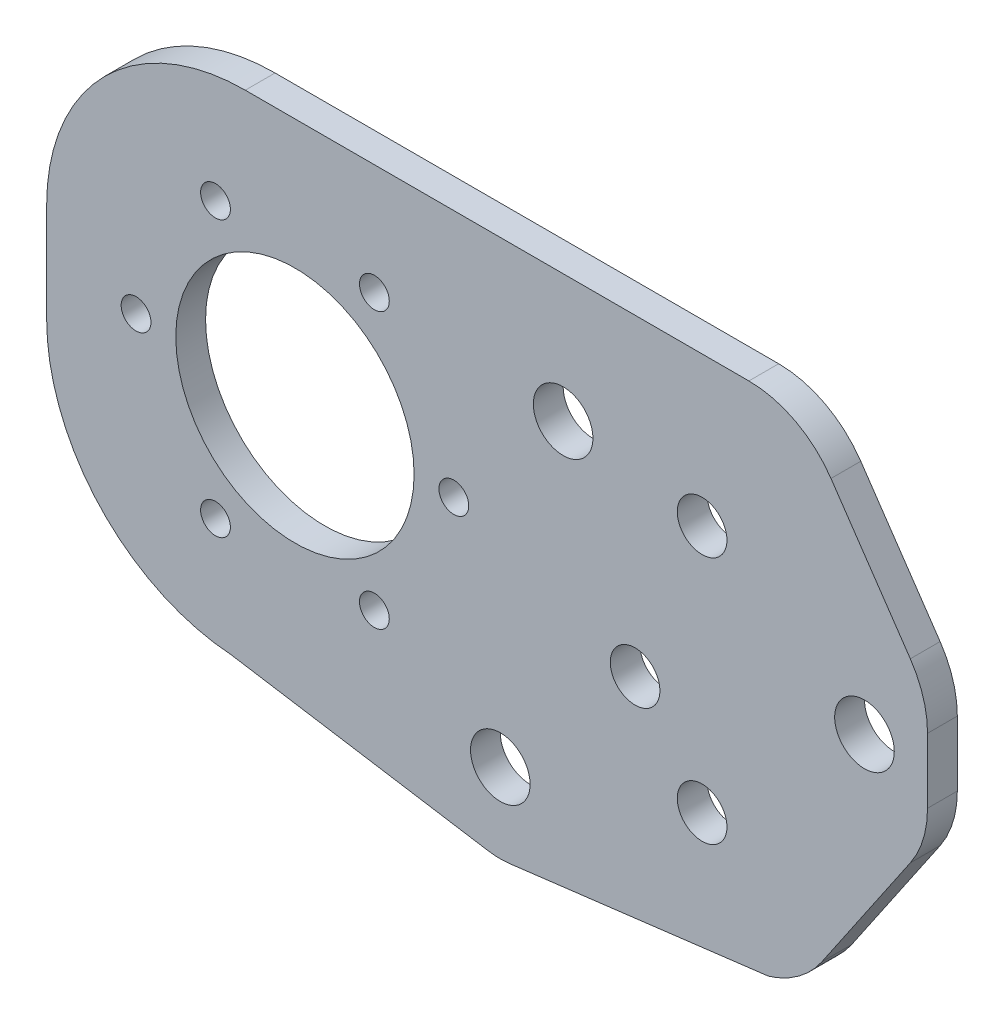
SolidWorks part; units mm, degrees
material "Gerais  - 6061-T6"
ref_plane "Plano frontal" through (0, 0, 0) normal (0, 0, 1) x (1, 0, 0)
ref_plane "Plano superior" through (0, 0, 0) normal (0, 1, 0) x (1, 0, 0)
ref_plane "Plano direito" through (0, 0, 0) normal (1, 0, 0) x (0, 0, -1)
sketch "Esboço1" plane through (0, 0, 0) normal (0, 0, 1) x (1, 0, 0)
  line L0 (56, 50) -> (56, 0) construction
  line L1 (0, 0) -> (76, 0)
  line L2 (0, 0) -> (0, 50)
  line L3 (0, 50) -> (76, 50)
  line L4 (76, 0) -> (76, 50)
  line L5 (66, 50) -> (66, 18.5) construction
  line L6 (65.25, 50) -> (65.25, 18.5) construction
  line L7 (59.25, 12.5) -> (25, 12.5) construction
  circle A0 centre (25, 25) radius 16 construction
  circle A1 centre (59.25, 18.5) radius 9.75 construction
  circle A2 centre (59.25, 18.5) radius 6 construction
  circle A3 centre (25, 25) radius 12.5 construction
  circle A4 centre (59.25, 18.5) radius 2.5
  circle A5 centre (25, 25) radius 12
  circle A6 centre (17, 38.8564) radius 1.5
  circle A7 centre (33, 38.8564) radius 1.5
  circle A8 centre (41, 25) radius 1.5
  circle A9 centre (33, 11.1436) radius 1.5
  circle A10 centre (17, 11.1436) radius 1.5
  circle A11 centre (9, 25) radius 1.5
  point P7 (41, 25)
  point P36 (25, 25)
  dimension "D1" = 32
  dimension "D5" = 12
  dimension "D6" = 19.5
  dimension "D9" = 25
  dimension "D10" = 5
  dimension "D13" = 24
  dimension "D14" = 3
  dimension "D2" = 25
  dimension "D3" = 35
  dimension "D4" = 20
  dimension "D7" = 0.75
  dimension "D8" = 10
  dimension "D11" = 25
  dimension "D12" = 50
  dimension "D15" = 6
extrude "Ressalto-extrusão1" add sketch "Esboço1" along normal blind 3
sketch "Esboço2" plane through (0, 0, 3) normal (0, 0, 1) x (1, 0, 0)
  line L0 (66, 50) -> (66, 0) construction
  line L1 (76, 50) -> (0, 50) construction
  line L2 (0, 0) -> (76, 0) construction
  line L3 (76, 0) -> (76, 50) construction
  circle A0 centre (66, 35) radius 2.5
  circle A1 centre (66, 15) radius 2.5
  dimension "D2" = 5
  dimension "D3" = 5
  dimension "D1" = 10
  dimension "D4" = 15
  dimension "D5" = 15
extrude "Corte-extrusão1" cut sketch "Esboço2" against normal blind 3
fillet "Filete1" radius 20 2 edges at (0, 0, 1.5) (0, 50, 1.5)
sketch "Esboço3" plane through (0, 0, 3) normal (0, 0, 1) x (1, 0, 0)
  circle A0 centre (66, 15) radius 2.5 construction
  circle A1 centre (66, 35) radius 2.5 construction
  circle A2 centre (66, 15) radius 2.5
  circle A3 centre (66, 35) radius 2.5
extrude "Ressalto-extrusão2" add sketch "Esboço3" against normal through all
sketch "Esboço5" plane through (0, 0, 0) normal (0, 0, -1) x (-1, 0, 0)
  circle A1 centre (-48, 43.65) radius 3 construction
  circle A2 centre (-45.6807, 3.8073) radius 3
  circle A3 centre (-48, 43.65) radius 3 construction
  circle A4 centre (-52.0071, 37.1424) radius 3
  circle A5 centre (-25, 25) radius 29.6112 construction
  circle A6 centre (-59.25, 18.5) radius 11 construction
  point P1 (-45.6808, 3.8073)
  dimension "D1" = 22
  dimension "D2" = 20
  dimension "D3" = 20
extrude "Corte-extrusão2" cut sketch "Esboço5" against normal through all
sketch "Esboço4" plane through (0, 0, 0) normal (0, 0, -1) x (-1, 0, 0)
  line L0 (-20, 0) -> (-76, 0) construction
  line L1 (-20, 0) -> (-76, 0)
  line L2 (-72.6649, -0.9251) -> (-46.6606, -4.1338)
  line L3 (-44.4129, -4.0929) -> (-15.4797, 0.5503)
  line L5 (-78.9768, 45.6286) -> (-86.9656, 33.897)
  line L6 (-73.1059, -0.8046) -> (-50.0089, -7.2259)
  line L7 (-46.1556, -7.2697) -> (-15.0816, 0.6142)
  line L8 (0, 20) -> (0, 30)
  line L9 (-20, 50) -> (-70.7112, 50)
  line L13 (0, 20) -> (0, 30)
  line L14 (-20, 50) -> (-70.7112, 50)
  line L28 (-78.9768, 45.6286) -> (-86.9656, 33.897)
  line L29 (-88.7, 28.2685) -> (-88.7, 21.7315)
  line L30 (-88.7, 28.2685) -> (-88.7, 21.7315)
  line L31 (-86.9656, 16.103) -> (-78.0603, 3.0256)
  line L32 (-86.9656, 16.103) -> (-78.0603, 3.0256)
  line L42 (-76, 0.8122) -> (-76, 0.7319)
  line L43 (-76, 0.8122) -> (-76, 0.7319)
  arc A0 (-78.0603, 3.0256) -> (-72.6649, -0.9251) centre (-69.7947, 8.6541) ccw
  arc A1 (-15.4797, 0.5503) -> (-14.5787, 0.7488) centre (-16.7476, 8.4505) ccw
  arc A2 (-46.6606, -4.1338) -> (-44.4129, -4.0929) centre (-45.6807, 3.8073) ccw
  arc A3 (-50.0089, -7.2259) -> (-46.1556, -7.2697) centre (-48, 0) ccw
  arc A4 (-15.0816, 0.6142) -> (0, 20) centre (-20, 20) ccw
  arc A5 (0, 30) -> (-20, 50) centre (-20, 30) ccw
  arc A7 (-14.5787, 0.7488) -> (0, 20) centre (-20, 20) ccw
  arc A8 (0, 30) -> (-20, 50) centre (-20, 30) ccw
  arc A22 (-70.7112, 50) -> (-78.9768, 45.6286) centre (-70.7112, 40) ccw
  arc A23 (-70.7112, 50) -> (-78.9768, 45.6286) centre (-70.7112, 40) ccw
  arc A24 (-86.9656, 33.897) -> (-88.7, 28.2685) centre (-78.7, 28.2685) ccw
  arc A25 (-86.9656, 33.897) -> (-88.7, 28.2685) centre (-78.7, 28.2685) ccw
  arc A26 (-88.7, 21.7315) -> (-86.9656, 16.103) centre (-78.7, 21.7315) ccw
  arc A27 (-88.7, 21.7315) -> (-86.9656, 16.103) centre (-78.7, 21.7315) ccw
  arc A58 (-78.0603, 3.0256) -> (-76, 0.8122) centre (-69.7947, 8.6541) ccw
  arc A60 (-76, 0.7319) -> (-73.1059, -0.8046) centre (-70.3513, 7.878) ccw
  point P25 (-45.6807, 3.8073)
  point P26 (-45.5353, -4.1927)
  line M13 (-76, 0) -> (-20, 0)
  arc M14 (-20, 0) -> (0, 20) centre (-20, 20) ccw
  dimension "D2" = 8
  dimension "D1" = 0
extrude "Ressalto-extrusão3" add sketch "Esboço4" against normal through all contours M14 M13 region at (47.6867, -1.4435, 0)
sketch "Esboço6" plane through (0, 0, 3) normal (0, 0, 1) x (1, 0, 0)
  line L0 (76, 50) -> (88.7, 31.35)
  line L1 (88.7, 31.35) -> (88.7, 18.65)
  line L2 (88.7, 18.65) -> (76, 0)
  line L3 (76, 0) -> (76, 50) construction
  line L4 (25, 25) -> (88.7, 25) construction
  circle A0 centre (82.35, 25) radius 3
  line M6 (76, 0) -> (76, 50)
  dimension "D2" = 6
  dimension "D3" = 12.7
  dimension "D4" = 6.35
extrude "Ressalto-extrusão4" add sketch "Esboço6" against normal through all contours L4 A0 L1 L0 M6 | L4 L2 L1 A0 M6 region at (80.9945, 34.3345, 3) region at (80.9945, 15.6655, 3)
fillet "Filete2" radius 10 4 edges at (88.7, 18.65, 1.5) (88.7, 31.35, 1.5) (76, 50, 1.5) (76, 0, 1.5)
sketch "Esboço7" plane through (0, 0, 3) normal (0, 0, 1) x (1, 0, 0)
  circle A0 centre (66, 35) radius 2.5
  circle A1 centre (66, 10) radius 2.5
  circle A2 centre (25, 25) radius 12 construction
  dimension "D1" = 5
  dimension "D2" = 25
  dimension "D3" = 41
  dimension "D4" = 15
extrude "Corte-extrusão3" cut sketch "Esboço7" against normal blind 10
